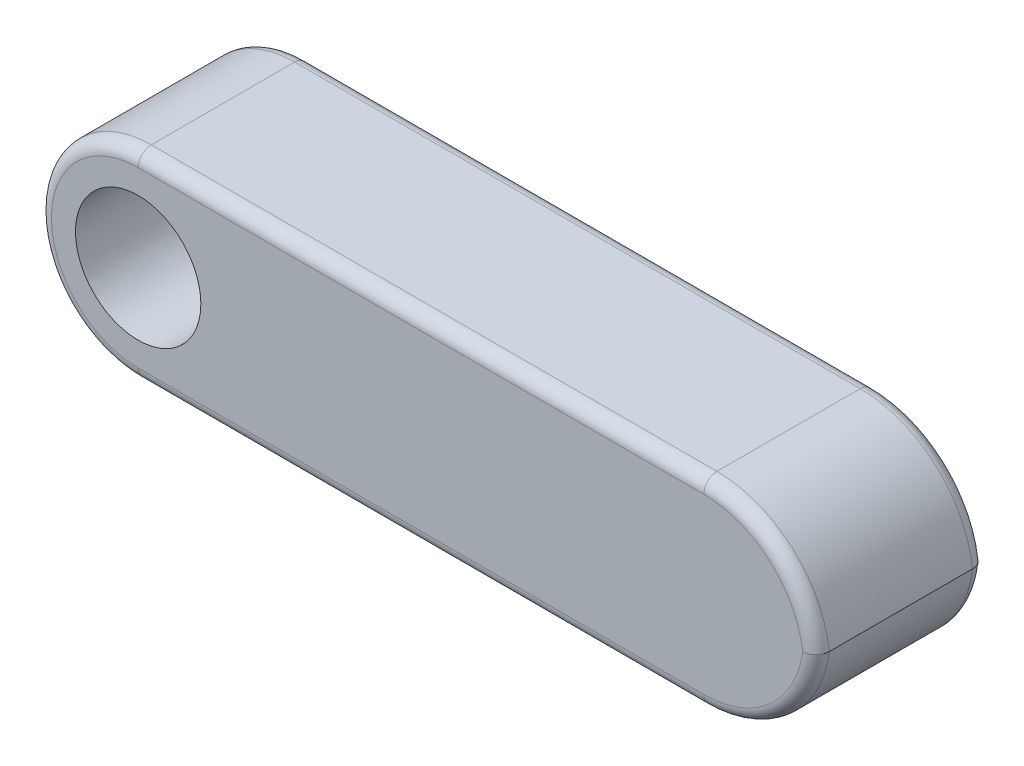
SolidWorks part; units mm, degrees
ref_plane "Front Plane" through (0, 0, 0) normal (0, 0, 1) x (1, 0, 0)
ref_plane "Top Plane" through (0, 0, 0) normal (0, 1, 0) x (1, 0, 0)
ref_plane "Right Plane" through (0, 0, 0) normal (1, 0, 0) x (0, 0, -1)
sketch "Sketch1" plane through (0, 0, 0) normal (0, 0, 1) x (1, 0, 0)
  line L0 (0, 6.731) -> (45.72, 6.731)
  line L1 (0, -6.731) -> (45.72, -6.731)
  line L2 (45.72, 6.731) -> (45.72, -6.731)
  circle A0 centre (0, 0) radius 4.2227
  circle A1 centre (0, 0) radius 6.731
  dimension "D1" = 8.4455
  dimension "D2" = 13.462
  dimension "D3" = 45.72
extrude "Boss-Extrude1" add sketch "Sketch1" along normal blind 11.43 contours A1 L1 L2 L0 | A1 A0 region at (25.4753, 0, 0) region at (4.6249, 4.6249, 0)
fillet "Front Fillet" radius 7.62 2 edges at (45.72, -6.731, 5.715) (45.72, 6.731, 5.715)
fillet "Side Fillet" radius 0.889 10 edges at (19.05, 6.731, 0) (-6.731, 0, 0) (19.05, -6.731, 0) (43.1641, -4.8048, 0) (43.1641, 4.8048, 0) (-6.731, 0, 11.43) (19.05, 6.731, 11.43) (43.1641, 4.8048, 11.43) (43.1641, -4.8048, 11.43) (19.05, -6.731, 11.43)
equation "\"UpperAxleDiameter\"=0.3325"
equation "\"D1@Sketch1\"=\"UpperAxleDiameter\""
equation "\"toeLength\"=1.8"
equation "\"D3@Sketch1\"=\"toeLength\""
equation "\"toeWidth\"= 0.5"
